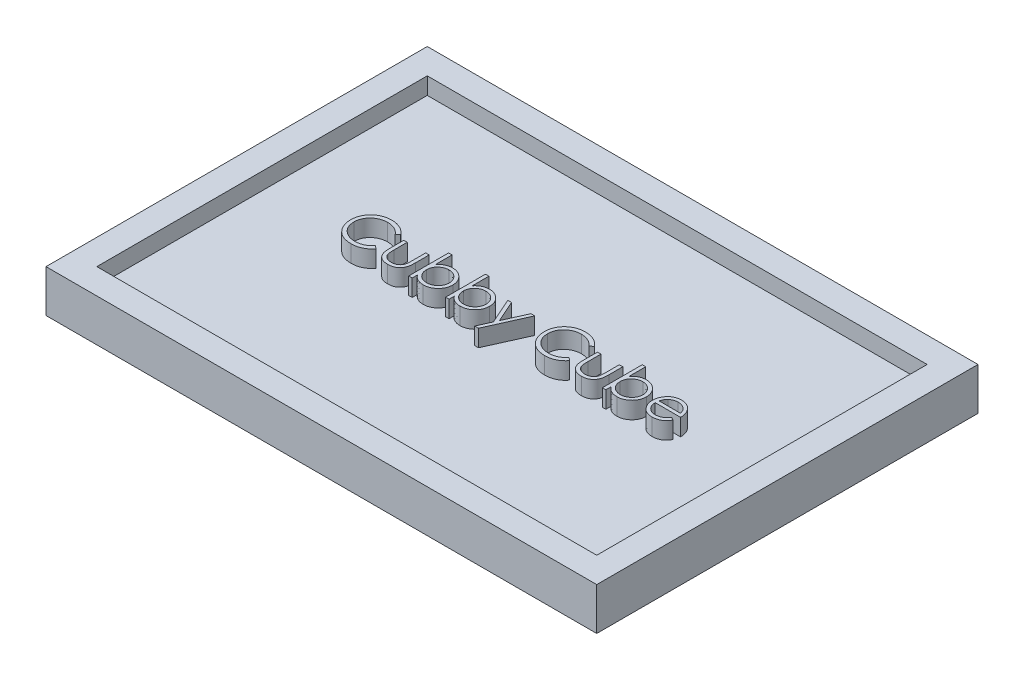
SolidWorks part; units mm, degrees
ref_plane "Front Plane" through (0, 0, 0) normal (0, 0, 1) x (1, 0, 0)
ref_plane "Top Plane" through (0, 0, 0) normal (0, 1, 0) x (1, 0, 0)
ref_plane "Right Plane" through (0, 0, 0) normal (1, 0, 0) x (0, 0, -1)
sketch "Sketch1" plane through (0, 0, 0) normal (0, 1, 0) x (1, 0, 0)
  line L1 (0, 0) -> (82.55, 0)
  line L2 (0, 0) -> (0, 57.15)
  line L3 (0, 57.15) -> (82.55, 57.15)
  line L4 (82.55, 0) -> (82.55, 57.15)
  dimension "D1" = 82.55
  dimension "D2" = 57.15
extrude "Boss-Extrude1" add sketch "Sketch1" along normal blind 6.35
shell "Shell1" thickness 3.81 removed face at (41.275, 6.35, -28.575)
sketch "Sketch2" plane through (0, 3.81, 0) normal (0, 1, 0) x (1, 0, 0)
  text T0 "Cubby Cube" font "Century Gothic" height in points 22
extrude "Boss-Extrude2" add sketch "Sketch2" along normal blind 2.54
